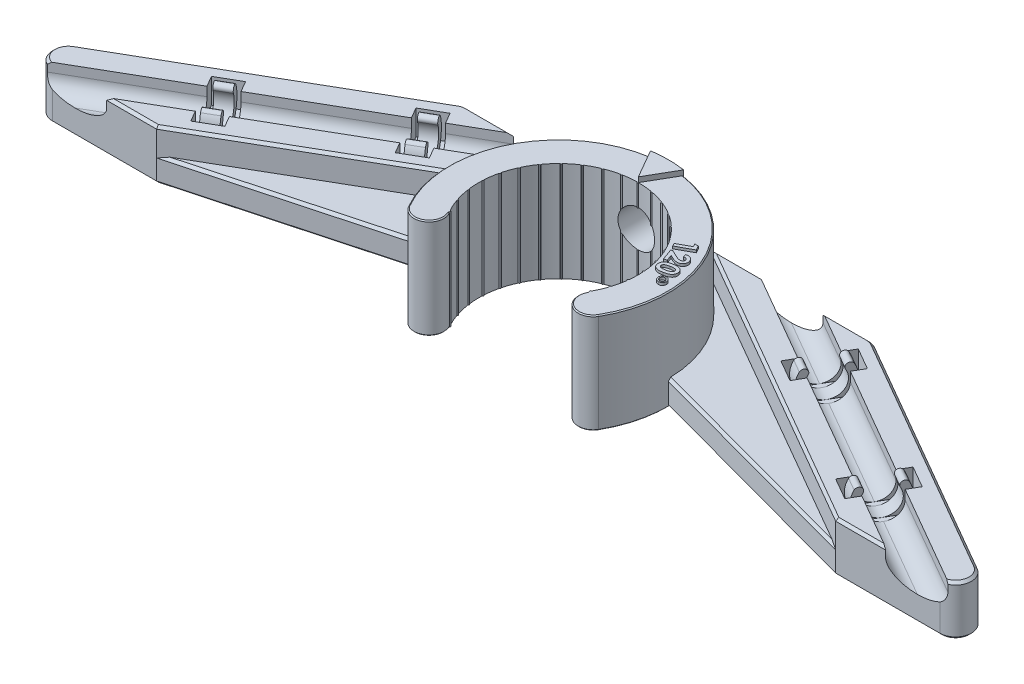
SolidWorks part; units mm, degrees
ref_plane "Front Plane" through (0, 0, 0) normal (0, 0, 1) x (1, 0, 0)
ref_plane "Top Plane" through (0, 0, 0) normal (0, 1, 0) x (1, 0, 0)
ref_plane "Right Plane" through (0, 0, 0) normal (1, 0, 0) x (0, 0, -1)
sketch "Sketch1" plane through (0, 0, 0) normal (0, 1, 0) x (1, 0, 0)
  line L0 (0, -75.7587) -> (0, 75.3111) construction
  line L1 (0, 36.2272) -> (116.0914, -30.7982) construction
  line L2 (0, 36.2272) -> (-89.4166, -15.3975) construction
  line L3 (-14.25, 28) -> (14.25, 28) construction
  line L4 (0, 0) -> (-37.046, -21.3885) construction
  line L5 (0, 0) -> (40.2254, -23.2241) construction
  line L6 (30.9923, 22) -> (90.7481, -12.5)
  line L7 (78.0481, -12.5) -> (18.2923, 22)
  line L8 (-99.8458, -12.5) -> (125.1246, -12.5) construction
  line L9 (-90.7481, -12.5) -> (-30.9923, 22)
  line L10 (-78.0481, -12.5) -> (-18.2923, 22)
  line L11 (-30.9923, 22) -> (30.9923, 22)
  line L12 (-40.9923, 22) -> (-100.7481, -12.5)
  line L13 (40.9923, 22) -> (100.7481, -12.5)
  line L14 (-30.9923, 22) -> (-40.9923, 22)
  line L15 (30.9923, 22) -> (40.9923, 22)
  line L16 (-68.0481, -12.5) -> (-22, 0)
  line L17 (-78.0481, -12.5) -> (-68.0481, -12.5)
  line L18 (-100.7481, -12.5) -> (-90.7481, -12.5)
  line L19 (-90.7481, -12.5) -> (-78.0481, -12.5)
  line L20 (78.0481, -12.5) -> (100.7481, -12.5)
  line L21 (40.9923, 22) -> (30.9923, 22)
  line L22 (78.0481, -12.5) -> (68.0481, -12.5)
  line L23 (68.0481, -12.5) -> (22, 0)
  line L24 (-68.0481, -12.5) -> (-8.2923, 22)
  line L25 (8.2923, 22) -> (68.0481, -12.5)
  line L26 (68.0481, -12.5) -> (78.0481, -12.5)
  arc A0 (13.8564, -8) -> (-13.8564, -8) centre (0, 0) ccw
  arc A1 (19.0526, -11) -> (-19.0526, -11) centre (0, 0) ccw
  arc A2 (-13.8564, -8) -> (-19.0526, -11) centre (-16.4545, -9.5) cw
  arc A3 (19.0526, -11) -> (13.8564, -8) centre (16.4545, -9.5) cw
  dimension "D1" = 32
  dimension "D6" = 6
  dimension "D2" = 60
  dimension "D3" = 60
  dimension "D4" = 5
  dimension "D5" = 28.5
  dimension "D7" = 60
  dimension "D8" = 60
  dimension "D9" = 3.175
  dimension "D10" = 3.175
  dimension "D11" = 3.175
  dimension "D12" = 3.175
  dimension "D13" = 6
  dimension "D14" = 5
  dimension "D15" = 5
  dimension "D17" = 5
extrude "Boss-Extrude1" add sketch "Sketch1" along normal blind 5 contours A3 A1 A2 A0 | A1 L23 L22 L7 L11 | L7 L20 L6 L11 | L6 L20 L13 L15 | A1 L11 L10 L17 L16 | L9 L19 L10 L11 | L12 L18 L9 L14 | A1 L11 L24 L16 | A1 L23 L25 L11 | L17 L24 L11 L10 | L11 L25 L22 L7 region at (65.8702, 0, -4.75) region at (54.5202, 0, -4.75) region at (43.1702, 0, -4.75) region at (34.6102, 0, -2.3958) region at (-34.6102, 0, -2.3958) region at (15.161, 0, -15.161) region at (-43.1702, 0, -4.75) region at (-54.5202, 0, -4.75) region at (-65.8702, 0, -4.75)
extrude "Boss-Extrude2" add sketch "Sketch1<3>" along normal blind 5 from surface contours A3 A1 A2 A0 | L12 L18 L9 L14 | L6 L20 L13 L15 | L17 L24 L11 L10 | L11 L25 L22 L7 region at (65.8702, 0, -4.75) region at (43.1702, 0, -4.75) region at (15.161, 0, -15.161) region at (-43.1702, 0, -4.75) region at (-65.8702, 0, -4.75) starting at face at (0, 5, 2.132)
sketch "Sketch1<3>" plane through (0, 0, 0) normal (0, 1, 0) x (1, 0, 0) same geometry as "Sketch1"
extrude "Boss-Extrude5" add sketch "Sketch1<4>" along normal blind 10 from surface contours A3 A1 A2 A0 region at (15.161, 0, -15.161) starting at face at (0, 10, -3.451)
sketch "Sketch1<4>" plane through (0, 0, 0) normal (0, 1, 0) x (1, 0, 0) same geometry as "Sketch1"
fillet "Fillet1" radius 3.175 4 edges at (48.1702, 5, -4.75) (60.8702, 5, -4.75) (-48.1702, 5, -4.75) (-60.8702, 5, -4.75)
sketch "Sketch2" plane through (0, 10, 0) normal (0, 1, 0) x (1, 0, 0)
  line L0 (-40.9026, 19.1651) -> (-35.2276, 9.3357)
  line L1 (-35.2276, 9.3357) -> (-39.5577, 6.8357)
  line L2 (-39.5577, 6.8357) -> (-45.2327, 16.6651)
  line L3 (-45.2327, 16.6651) -> (-40.9026, 19.1651)
  line L4 (-90.7481, -12.5) -> (-30.9923, 22) construction
  line L5 (-78.0481, -12.5) -> (-18.2923, 22) construction
  line L6 (-71.2134, 1.6651) -> (-66.8833, 4.1651)
  line L7 (-66.8833, 4.1651) -> (-61.2083, -5.6643)
  line L8 (-61.2083, -5.6643) -> (-65.5384, -8.1643)
  line L9 (-65.5384, -8.1643) -> (-71.2134, 1.6651)
  line L10 (0, 62.2666) -> (0, -32.3979) construction
  line L11 (0, -75.7587) -> (0, 75.3111) construction
  line L12 (65.5384, -8.1643) -> (71.2134, 1.6651)
  line L13 (61.2083, -5.6643) -> (65.5384, -8.1643)
  line L14 (66.8833, 4.1651) -> (61.2083, -5.6643)
  line L15 (71.2134, 1.6651) -> (66.8833, 4.1651)
  line L16 (39.5577, 6.8357) -> (45.2327, 16.6651)
  line L17 (35.2276, 9.3357) -> (39.5577, 6.8357)
  line L18 (40.9026, 19.1651) -> (35.2276, 9.3357)
  line L19 (45.2327, 16.6651) -> (40.9026, 19.1651)
  dimension "D1" = 2.5
  dimension "D2" = 2.5
  dimension "D3" = 5
  dimension "D4" = 10
  dimension "D5" = 2
extrude "Cut-Extrude1" cut sketch "Sketch2" against normal blind 5
sketch "Sketch3" plane through (-22.3782, 0, 12.9201) normal (-0.866, 0, 0.5) x (0.5, 0, 0.866)
  line L0 (-31.3737, 5) -> (-31.3737, 17.4701) construction
  line L1 (-31.3737, 8.175) -> (-38.8093, 12.4679) construction
  line L2 (-31.3737, 8.175) -> (-25.1843, 11.7484) construction
  line L3 (-23.6041, 5) -> (-42.1182, 5) construction
  line L5 (-34.8052, 5) -> (-27.9422, 5)
  arc A0 (-34.1233, 9.7625) -> (-28.6241, 9.7625) centre (-31.3737, 8.175) ccw
  arc A1 (-31.3737, 5) -> (-28.1987, 8.175) centre (-31.3737, 8.175) ccw construction
  arc A2 (-35.4224, 10.5125) -> (-34.8052, 5) centre (-31.3737, 8.175) ccw
  arc A3 (-35.4224, 10.5125) -> (-34.1233, 9.7625) centre (-34.7729, 10.1375) cw
  arc A4 (-28.6241, 9.7625) -> (-27.325, 10.5125) centre (-27.9746, 10.1375) cw
  arc A5 (-27.9422, 5) -> (-27.325, 10.5125) centre (-31.3737, 8.175) ccw
  point P21 (0, 0)
  line M6 (-34.5487, 8.175) -> (-34.5487, 10)
  line M7 (-34.5487, 10) -> (-37.0487, 10)
  line M9 (-37.0487, 5) -> (-31.3737, 5)
  arc M10 (-31.3737, 5) -> (-34.5487, 8.175) centre (-31.3737, 8.175) cw
  dimension "D1" = 1.5
  dimension "D2" = 60
  dimension "D3" = 60
extrude "Boss-Extrude3" add sketch "Sketch3" along normal blind 3 from offset 1 contours A2 M7 M9 M10 M6 | A3 A2 A0 M7 M6 | L5 A5 A4 A0 region at (-39.7973, 7.2331, -17.2508) region at (-36.3431, 7.6768, -11.2679) region at (-39.7284, 10.1863, -17.1313)
extrude "Boss-Extrude4" add sketch "Sketch3<4>" along normal blind 3 from offset 31 contours A3 A2 A0 M7 M6 | A2 M7 M9 M10 M6 | L5 A5 A4 A0 region at (-39.7973, 7.2331, -17.2508) region at (-36.3431, 7.6768, -11.2679) region at (-39.7284, 10.1863, -17.1313)
sketch "Sketch3<4>" plane through (-22.3782, 0, 12.9201) normal (-0.866, 0, 0.5) x (0.5, 0, 0.866) same geometry as "Sketch3"
mirror "Mirror1" about plane through (0, 0, 0) normal (1, 0, 0) of "Boss-Extrude4", "Boss-Extrude3"
fillet "Fillet2" radius 3.175 4 edges at (-40.9923, 5, -22) (40.9923, 5, -22) (100.7481, 5, 12.5) (-100.7481, 5, 12.5)
sketch "Sketch4" plane through (0, 20, 0) normal (0, 1, 0) x (1, 0, 0)
  line L0 (0, 0) -> (0, 37.7856) construction
  line L1 (0, 16) -> (3.3187, 21.7482)
  line L2 (0, 16) -> (-3.3187, 21.7482)
  arc A0 (19.0526, -11) -> (-19.0526, -11) centre (0, 0) ccw construction
  arc A1 (13.8564, -8) -> (-13.8564, -8) centre (0, 0) ccw construction
  arc A2 (3.3187, 21.7482) -> (-3.3187, 21.7482) centre (0, 0) ccw
  point P3 (0, 0)
  dimension "D1" = 30
  dimension "D2" = 30
extrude "Boss-Extrude6" add sketch "Sketch4" along normal blind 1
sketch "Sketch5" plane through (0, 20, 0) normal (0, 1, 0) x (1, 0, 0)
  line L0 (-13.8564, -8) -> (-13.789, -7.7592)
  line L1 (-13.789, -7.7592) -> (-14.0298, -7.6919)
  line L2 (-15.1117, -5.2571) -> (-15.0003, -5.0332)
  line L3 (-15.0003, -5.0332) -> (-15.2242, -4.9219)
  line L4 (-15.8298, -2.3273) -> (-15.6784, -2.1283)
  line L5 (-15.6784, -2.1283) -> (-15.8774, -1.9769)
  line L6 (-15.9853, 0.6852) -> (-15.7993, 0.8522)
  line L7 (-15.7993, 0.8522) -> (-15.9663, 1.0383)
  line L8 (-15.5726, 3.6734) -> (-15.3585, 3.8025)
  line L9 (-15.3585, 3.8025) -> (-15.4876, 4.0166)
  line L10 (-14.6064, 6.531) -> (-14.3719, 6.6176)
  line L11 (-14.3719, 6.6176) -> (-14.4585, 6.8521)
  line L12 (-13.121, 9.1564) -> (-12.8744, 9.1975)
  line L13 (-12.8744, 9.1975) -> (-12.9155, 9.4441)
  line L14 (-11.1692, 11.4564) -> (-10.9193, 11.4505)
  line L15 (-10.9193, 11.4505) -> (-10.9133, 11.7004)
  line L16 (-8.8204, 13.3492) -> (-8.576, 13.2964)
  line L17 (-8.576, 13.2964) -> (-8.5233, 13.5408)
  line L18 (-6.1581, 14.7675) -> (-5.928, 14.6698)
  line L19 (-5.928, 14.6698) -> (-5.8303, 14.8999)
  line L20 (-3.2769, 15.6608) -> (-3.0692, 15.5217)
  line L21 (-3.0692, 15.5217) -> (-2.9301, 15.7294)
  line L22 (-0.2792, 15.9976) -> (-0.1013, 15.8219)
  line L23 (-0.1013, 15.8219) -> (0.0743, 15.9998)
  line L24 (2.7284, 15.7657) -> (2.8701, 15.5598)
  line L25 (2.8701, 15.5598) -> (3.076, 15.7015)
  line L26 (5.639, 14.9734) -> (5.7396, 14.7445)
  line L27 (5.7396, 14.7445) -> (5.9684, 14.8451)
  line L28 (8.3492, 13.6489) -> (8.405, 13.4052)
  line L29 (8.405, 13.4052) -> (8.6487, 13.4611)
  line L30 (10.7626, 11.8392) -> (10.7717, 11.5894)
  line L31 (10.7717, 11.5894) -> (11.0215, 11.5985)
  line L32 (12.7934, 9.6088) -> (12.7555, 9.3616)
  line L33 (12.7555, 9.3616) -> (13.0026, 9.3237)
  line L34 (14.3696, 7.0367) -> (14.2859, 6.8011)
  line L35 (14.2859, 6.8011) -> (14.5215, 6.7175)
  line L36 (15.4349, 4.2146) -> (15.3086, 3.9989)
  line L37 (15.3086, 3.9989) -> (15.5243, 3.8725)
  line L38 (15.9517, 1.2427) -> (15.7871, 1.0545)
  line L39 (15.7871, 1.0545) -> (15.9752, 0.8899)
  line L40 (15.9014, -1.7734) -> (15.7044, -1.9273)
  line L41 (15.7044, -1.9273) -> (15.8583, -2.1243)
  line L42 (15.286, -4.7265) -> (15.0636, -4.8407)
  line L43 (15.0636, -4.8407) -> (15.1778, -5.0631)
  line L44 (14.1272, -7.5115) -> (13.8873, -7.582)
  line L45 (13.8873, -7.582) -> (13.9577, -7.8219)
  arc A0 (13.8564, -8) -> (0, 16) centre (0, 0) ccw construction
  arc A1 (0, 16) -> (-13.8564, -8) centre (0, 0) ccw construction
  arc A2 (13.9577, -7.8219) -> (14.1272, -7.5115) centre (0, 0) ccw
  arc A3 (0, 16) -> (-0.2792, 15.9976) centre (0, 0) ccw
  arc A4 (-14.0298, -7.6919) -> (-13.8564, -8) centre (0, 0) ccw
  arc A5 (-15.2242, -4.9219) -> (-15.1117, -5.2571) centre (0, 0) ccw
  arc A6 (-15.8774, -1.9769) -> (-15.8298, -2.3273) centre (0, 0) ccw
  arc A7 (-15.9663, 1.0383) -> (-15.9853, 0.6852) centre (0, 0) ccw
  arc A8 (-15.4876, 4.0166) -> (-15.5726, 3.6734) centre (0, 0) ccw
  arc A9 (-14.4585, 6.8521) -> (-14.6064, 6.531) centre (0, 0) ccw
  arc A10 (-12.9155, 9.4441) -> (-13.121, 9.1564) centre (0, 0) ccw
  arc A11 (-10.9133, 11.7004) -> (-11.1692, 11.4564) centre (0, 0) ccw
  arc A12 (-8.5233, 13.5408) -> (-8.8204, 13.3492) centre (0, 0) ccw
  arc A13 (-5.8303, 14.8999) -> (-6.1581, 14.7675) centre (0, 0) ccw
  arc A14 (-2.9301, 15.7294) -> (-3.2769, 15.6608) centre (0, 0) ccw
  arc A15 (0.0743, 15.9998) -> (0, 16) centre (0, 0) ccw
  arc A16 (3.076, 15.7015) -> (2.7284, 15.7657) centre (0, 0) ccw
  arc A17 (5.9684, 14.8451) -> (5.639, 14.9734) centre (0, 0) ccw
  arc A18 (8.6487, 13.4611) -> (8.3492, 13.6489) centre (0, 0) ccw
  arc A19 (11.0215, 11.5985) -> (10.7626, 11.8392) centre (0, 0) ccw
  arc A20 (13.0026, 9.3237) -> (12.7934, 9.6088) centre (0, 0) ccw
  arc A21 (14.5215, 6.7175) -> (14.3696, 7.0367) centre (0, 0) ccw
  arc A22 (15.5243, 3.8725) -> (15.4349, 4.2146) centre (0, 0) ccw
  arc A23 (15.9752, 0.8899) -> (15.9517, 1.2427) centre (0, 0) ccw
  arc A24 (15.8583, -2.1243) -> (15.9014, -1.7734) centre (0, 0) ccw
  arc A25 (15.1778, -5.0631) -> (15.286, -4.7265) centre (0, 0) ccw
  dimension "D2" = 0.25
  dimension "D1" = 90
  dimension "D3" = 23
extrude "Boss-Extrude7" add sketch "Sketch5" against normal up to surface (20 mm away) up to face at (0, 0, -0.2128)
sketch "Sketch8" plane through (0, 0, 0) normal (0, -1, 0) x (1, 0, 0)
  line L0 (3.4641, -22) -> (-3.4641, -22)
  line L2 (0, -16) -> (-3.3187, -21.7482)
  line L3 (3.3187, -21.7482) -> (0, -16)
  line L4 (-1, -17.7321) -> (-3.4641, -22)
  line L5 (3.4641, -22) -> (1, -17.7321)
  line L8 (-1, -17.7321) -> (-1, -14.2679)
  line L9 (-1, -14.2679) -> (1, -14.2679)
  line L10 (1, -17.7321) -> (1, -14.2679)
  line L11 (0, -16) -> (1, -14.2679) construction
  line L12 (-1, -14.2679) -> (0, -16) construction
  arc A1 (-3.3187, -21.7482) -> (3.3187, -21.7482) centre (0, 0) ccw
  point P10 (0, 0)
  dimension "D2" = 2
  dimension "D3" = 3.4641
  dimension "D1" = 0
extrude "Cut-Extrude4" cut sketch "Sketch8" against normal blind 1
chamfer "Chamfer1" distance 0.5 angle 45 27 edges at (-91.9656, 0, 10.1468) (-78.4734, 0, 12.5) (-45.024, 0, 6.25) (45.024, 0, 6.25) (78.4734, 0, 12.5) (91.9656, 0, 10.1468) (66.1077, 0, -7.4996) (40.9633, 0, -21.8918) (-40.9633, 0, -21.8918) (-66.1077, 0, -7.4996) (35.5669, 10, -22) (92.0707, 10, 9.4659) (40.9633, 10, -21.8918) (66.1077, 10, -7.4996) (-35.5669, 10, -22) (-92.0707, 10, 9.4659) (-40.9633, 10, -21.8918) (-66.1077, 10, -7.4996) (13.2923, 10, -22) (73.0481, 10, 12.5) (38.1702, 10, -4.75) (-13.2923, 10, -22) (-73.0481, 10, 12.5) (-38.1702, 10, -4.75) (45.024, 5, 6.25) (-45.024, 5, 6.25) (21.8028, 0, -22)
chamfer "Chamfer2" distance 0.2 angle 45 9 edges at (13.9074, 0, 7.9111) (14.9545, 0, 12.0981) (21.3162, 0, 5.4426) (-14.9545, 0, 12.0981) (-21.3162, 0, 5.4426) (14.9545, 20, 12.0981) (19.83, 20, -9.5273) (-14.9545, 20, 12.0981) (-19.83, 20, -9.5273)
sketch "Sketch6" plane through (0, 0, -22) normal (0, 0, -1) x (-1, 0, 0)
  line L0 (40.1416, 0) -> (3.1754, 0) construction
  circle A0 centre (0, 12) radius 3.675
  point P4 (0, 0)
  dimension "D1" = 7.35
  dimension "D2" = 12
extrude "Cut-Extrude2" cut sketch "Sketch6" against normal up to next
sketch "Sketch7" plane through (0, 20, 0) normal (0, 1, 0) x (1, 0, 0)
  circle A0 centre (0, 0) radius 16.98 construction
  text T0 "<b>120°</b>"
extrude "Boss-Extrude8" add sketch "Sketch7" along normal blind 0.5
